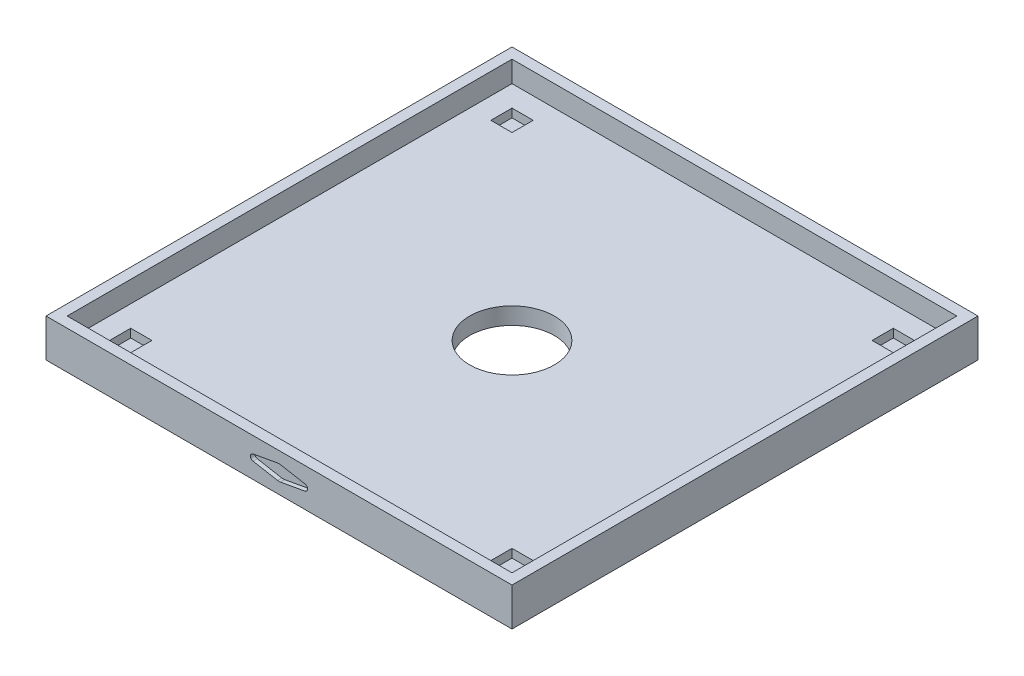
SolidWorks part; units mm, degrees
ref_plane "Front Plane" through (0, 0, 0) normal (0, 0, 1) x (1, 0, 0)
ref_plane "Top Plane" through (0, 0, 0) normal (0, 1, 0) x (1, 0, 0)
ref_plane "Right Plane" through (0, 0, 0) normal (1, 0, 0) x (0, 0, -1)
sketch "Sketch1" plane through (0, 0, 0) normal (0, 1, 0) x (1, 0, 0)
  line L1 (-110, -110) -> (110, -110)
  line L2 (-110, -110) -> (-110, 110)
  line L3 (-110, 110) -> (110, 110)
  line L4 (110, -110) -> (110, 110)
  line L5 (-110, -110) -> (110, 110) construction
  line L6 (-110, 110) -> (110, -110) construction
  point P0 (0, 0)
  dimension "D1" = 220
extrude "Boss-Extrude1" add sketch "Sketch1" along normal blind 18
sketch "Sketch2" plane through (0, 18, 0) normal (0, 1, 0) x (1, 0, 0)
  line L0 (110, 110) -> (-110, 110) construction
  line L1 (-105, -105) -> (105, -105)
  line L2 (-105, -105) -> (-105, 105)
  line L3 (-105, 105) -> (105, 105)
  line L4 (105, -105) -> (105, 105)
  line L5 (-105, -105) -> (105, 105) construction
  line L6 (-105, 105) -> (105, -105) construction
  point P1 (0, 0)
  dimension "D1" = 5
extrude "Cut-Extrude1" cut sketch "Sketch2" against normal blind 10
sketch "Sketch3" plane through (0, 0, 110) normal (0, 0, 1) x (1, 0, 0)
  line L0 (110, 18) -> (110, 0) construction
  line L1 (-110, 18) -> (-110, 0) construction
  line L2 (-12.2662, 10.4762) -> (-0.6443, 12.5724)
  line L3 (-12.2662, 7.5238) -> (-0.6443, 5.4276)
  line L4 (0.6443, 5.4276) -> (12.2662, 7.5238)
  line L5 (0.6443, 12.5724) -> (12.2663, 10.4762)
  arc A1 (-0.6443, 5.4276) -> (0.6443, 5.4276) centre (0, 9) ccw
  arc A2 (-12.2662, 10.4762) -> (-12.2662, 7.5238) centre (-12, 9) ccw
  arc A3 (12.2662, 7.5238) -> (12.2663, 10.4762) centre (12, 9) ccw
  arc A4 (0.6443, 12.5724) -> (-0.6443, 12.5724) centre (0, 9) ccw
  point P4 (110, 9)
  point P11 (-110, 9)
  dimension "D1" = 7.26
  dimension "D2" = 3
  dimension "D3" = 12
  dimension "D4" = 12
extrude "Cut-Extrude2" cut sketch "Sketch3" against normal blind 2
mirror "Mirror1" about plane through (0, 0, 0) normal (0, 0, 1) of "Cut-Extrude2"
sketch "Sketch4" plane through (0, 8, 0) normal (0, 1, 0) x (1, 0, 0)
  line L0 (105, 105) -> (-105, 105) construction
  line L1 (-105, 105) -> (-105, -105) construction
  line L3 (-95, 95) -> (-85, 95)
  line L4 (-95, 95) -> (-95, 85)
  line L5 (-95, 85) -> (-85, 85)
  line L6 (-85, 95) -> (-85, 85)
  line L7 (-95, 95) -> (-85, 85) construction
  line L8 (-95, 85) -> (-85, 95) construction
  point P0 (-90, 90)
  point P5 (-93.9517, 93.5178)
  point P6 (-87.4401, 88.2176)
  dimension "D1" = 10
  dimension "D2" = 10
  dimension "D3" = 10
extrude "Cut-Extrude3" cut sketch "Sketch4" against normal blind 4
mirror "Mirror2" about plane through (0, 0, 0) normal (1, 0, 0) of "Cut-Extrude3" second plane through (0, 0, 0) second plane normal (0, 0, 1)
sketch "Sketch5" plane through (0, 8, 0) normal (0, 1, 0) x (1, 0, 0)
  circle A0 centre (0, 0) radius 20
  dimension "D1" = 40
extrude "Cut-Extrude4" cut sketch "Sketch5" against normal through all
